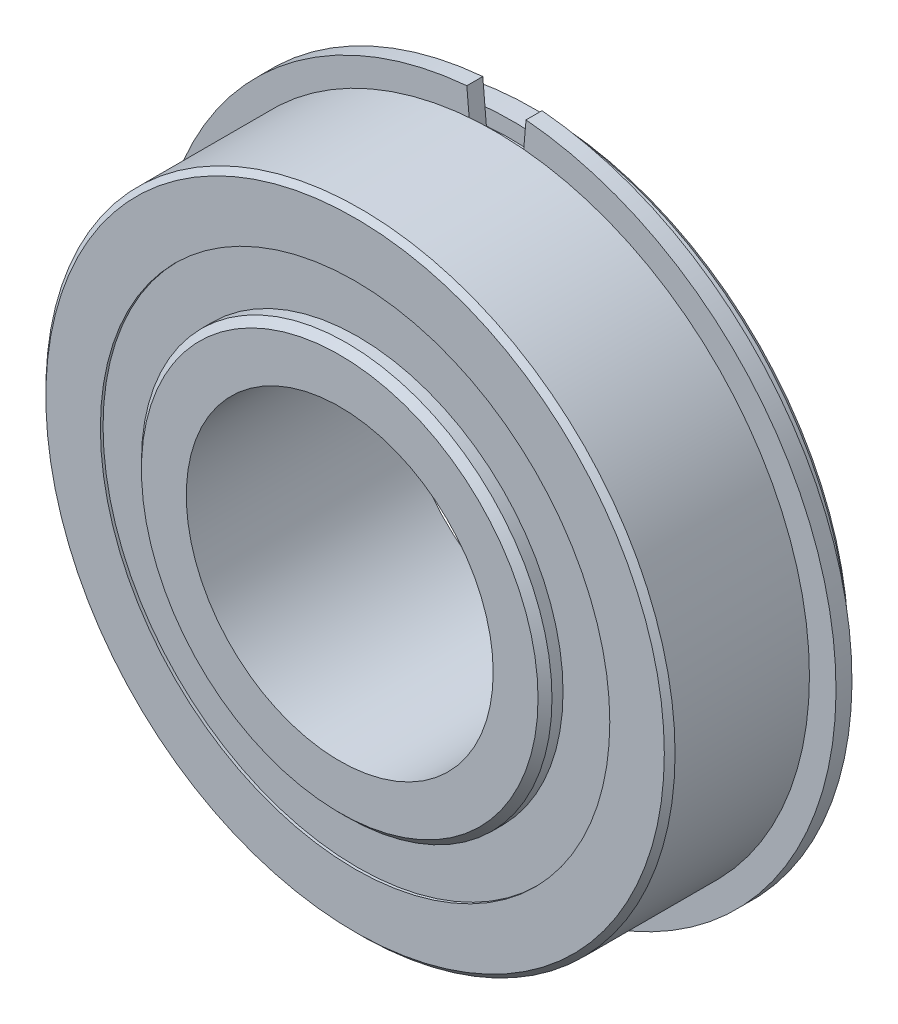
SolidWorks part; units mm, degrees
ref_plane "Front Plane" through (0, 0, 0) normal (0, 0, 1) x (1, 0, 0)
ref_plane "Top Plane" through (0, 0, 0) normal (0, 1, 0) x (1, 0, 0)
ref_plane "Right Plane" through (0, 0, 0) normal (1, 0, 0) x (0, 0, -1)
sketch "Sketch1" plane through (0, 0, 0) normal (1, 0, 0) x (0, 0, -1)
  line L0 (-11.1125, 0) -> (11.1125, 0) construction
  line L1 (0, 32.5437) -> (0, -32.5437) construction
  line L2 (8.9694, 32.5437) -> (-8.9694, 32.5437)
  line L3 (-8.9694, 32.5437) -> (-9.525, 31.9881)
  line L4 (-9.525, 31.9881) -> (-9.525, 26.348)
  line L5 (-9.525, 26.348) -> (-3.7042, 26.348)
  line L6 (9.525, 26.348) -> (3.7042, 26.348)
  line L7 (9.525, 31.9881) -> (9.525, 26.348)
  line L8 (8.9694, 32.5437) -> (9.525, 31.9881)
  line L9 (0, 28.4866) -> (0, 26.348) construction
  line L10 (0, 26.348) -> (0, 24.2094) construction
  line L11 (0, 32.5437) -> (0, 28.4866) construction
  line L12 (0, 15.875) -> (0, 19.9322) construction
  arc A0 (-3.7042, 26.348) -> (3.7042, 26.348) centre (0, 24.2094) cw
  circle A1 centre (0, 24.2094) radius 4.2772 construction
  point P14 (0, 15.875)
  dimension "Width" = 22.225
  dimension "OD" = 65.0875
  dimension "D1" = 45
  dimension "D2" = 0.5556
  dimension "Shaft Dia" = 31.75
  dimension "D3" = 7.4083
  dimension "bodywd" = 19.05
revolve "Revolve1" add sketch "Sketch1" angle 360 about L0
sketch "Sketch3" plane through (0, 0, 0) normal (1, 0, 0) x (0, 0, -1)
  line L1 (0, 32.5437) -> (0, -32.5437) construction
  line L2 (-10.3907, 21.2344) -> (-3.0731, 21.2344)
  line L3 (-10.3907, 21.2344) -> (-11.1125, 20.5126)
  line L4 (-13.1255, 0) -> (13.1933, 0) construction
  line L5 (-11.1125, 20.5126) -> (-11.1125, 15.875)
  line L6 (-11.1125, 15.875) -> (11.1125, 15.875)
  line L7 (3.0731, 21.2344) -> (10.3907, 21.2344)
  line L8 (-8.9694, 32.5437) -> (-9.525, 31.9881) construction
  line L10 (10.3907, 21.2344) -> (11.1125, 20.5126)
  line L12 (11.1125, 20.5126) -> (11.1125, 15.875)
  arc A0 (3.7042, 26.348) -> (-3.7042, 26.348) centre (0, 24.2094) ccw construction
  arc A1 (3.0731, 21.2344) -> (-3.0731, 21.2344) centre (0, 24.2094) cw
  circle A2 centre (0, 24.2094) radius 4.2772 construction
  dimension "inner ring OD" = 42.4688
  dimension "D2" = 1.0208
revolve "Revolve3" add sketch "Sketch3" angle 360 about L0
sketch "Sketch4" plane through (0, 0, 0) normal (1, 0, 0) x (0, 0, -1)
  line L0 (-4.2772, 24.2094) -> (4.2772, 24.2094)
  arc A2 (-4.2772, 24.2094) -> (4.2772, 24.2094) centre (0, 24.2094) cw
  arc A3 (3.7042, 26.348) -> (-3.7042, 26.348) centre (0, 24.2094) ccw construction
revolve "Revolve4" add sketch "Sketch4" angle 360 about L0
ref_axis "Axis1" through (0, 0, -11.1125) along (0, 0, 1)
pattern_circular "CirPattern1" count 8 every 45 about axis through (0, 0, -11.1125) along (0, 0, 1) of bodies 104
sketch "Sketch5" plane through (0, 0, 0) normal (1, 0, 0) x (0, 0, -1)
  line L0 (-9.525, 26.348) -> (-3.7042, 26.348) construction
  line L1 (-9.2472, 26.348) -> (-4.2772, 26.348)
  line L2 (-9.2472, 26.348) -> (-9.2472, 21.2344)
  line L3 (-9.2472, 21.2344) -> (-4.2772, 21.2344)
  line L4 (-4.2772, 26.348) -> (-4.2772, 21.2344)
  line L6 (9.525, 26.348) -> (3.7042, 26.348) construction
  line L7 (9.2472, 26.348) -> (4.2772, 26.348)
  line L8 (9.2472, 26.348) -> (9.2472, 21.2344)
  line L9 (9.2472, 21.2344) -> (4.2772, 21.2344)
  line L10 (4.2772, 26.348) -> (4.2772, 21.2344)
  line L12 (-8.9694, 32.5437) -> (-9.525, 31.9881) construction
  line L13 (-10.3907, 21.2344) -> (-3.0731, 21.2344) construction
  line L14 (3.0731, 21.2344) -> (10.3907, 21.2344) construction
  point P18 (-9.2472, 32.2659)
revolve "Revolve5" add sketch "Sketch5" angle 360 about L0
sketch "Sketch6" plane through (0, 0, 0) normal (1, 0, 0) x (0, 0, -1)
  line L0 (8.9694, 32.5437) -> (-8.9694, 32.5437) construction
  line L1 (6.7469, 32.5437) -> (4.9308, 32.5437)
  line L2 (6.7469, 32.5437) -> (6.7469, 30.8624)
  line L3 (6.7469, 30.8624) -> (4.9308, 30.8624)
  line L4 (4.9308, 32.5437) -> (4.9308, 30.8624)
  line L5 (9.525, 31.9881) -> (9.525, 26.348) construction
  line L6 (9.525, 26.348) -> (3.7042, 26.348) construction
  dimension "D1" = 2.7781
  dimension "D2" = 4.5145
  dimension "D3" = 1.8161
revolve "Cut-Revolve1" cut sketch "Sketch6" angle 360 about L0
sketch "Sketch7" plane through (0, 0, -6.7469) normal (0, 0, 1) x (1, 0, 0)
  line L0 (0, 0) -> (2.6898, 30.745) construction
  line L1 (2.6898, 30.745) -> (3.0616, 34.9945)
  line L2 (0, 0) -> (-2.6898, 30.745) construction
  line L3 (-2.6898, 30.745) -> (-3.0616, 34.9945)
  line L4 (0, 35.1282) -> (0, 0) construction
  circle A0 centre (0, 0) radius 30.8624 construction
  circle A1 centre (0, 0) radius 35.1282 construction
  arc A2 (-3.0616, 34.9945) -> (3.0616, 34.9945) centre (0, 0) ccw
  arc A3 (2.6898, 30.745) -> (-2.6898, 30.745) centre (0, 0) cw
  dimension "D1" = 10
  dimension "Ring OD" = 70.2564
extrude "Extrude1" add sketch "Sketch7" along normal blind 1.651 separate body
equation "\"D2@Sketch1\" = \"Width@Sketch1\"*.025"
equation "\"D3@Sketch1\" = \"Width@Sketch1\"/3"
equation "\"D2@CirPattern1\" = 360/\"Balls@CirPattern1\""
equation "\"D1@Sketch6\" = (\"Width@Sketch1\"/2)*.25"
equation "\"D2@Sketch6\" = \"D1@Sketch6\"*1.625"
equation "\"D3@Sketch6\" = \"ring thk@Extrude1\"*1.1"
